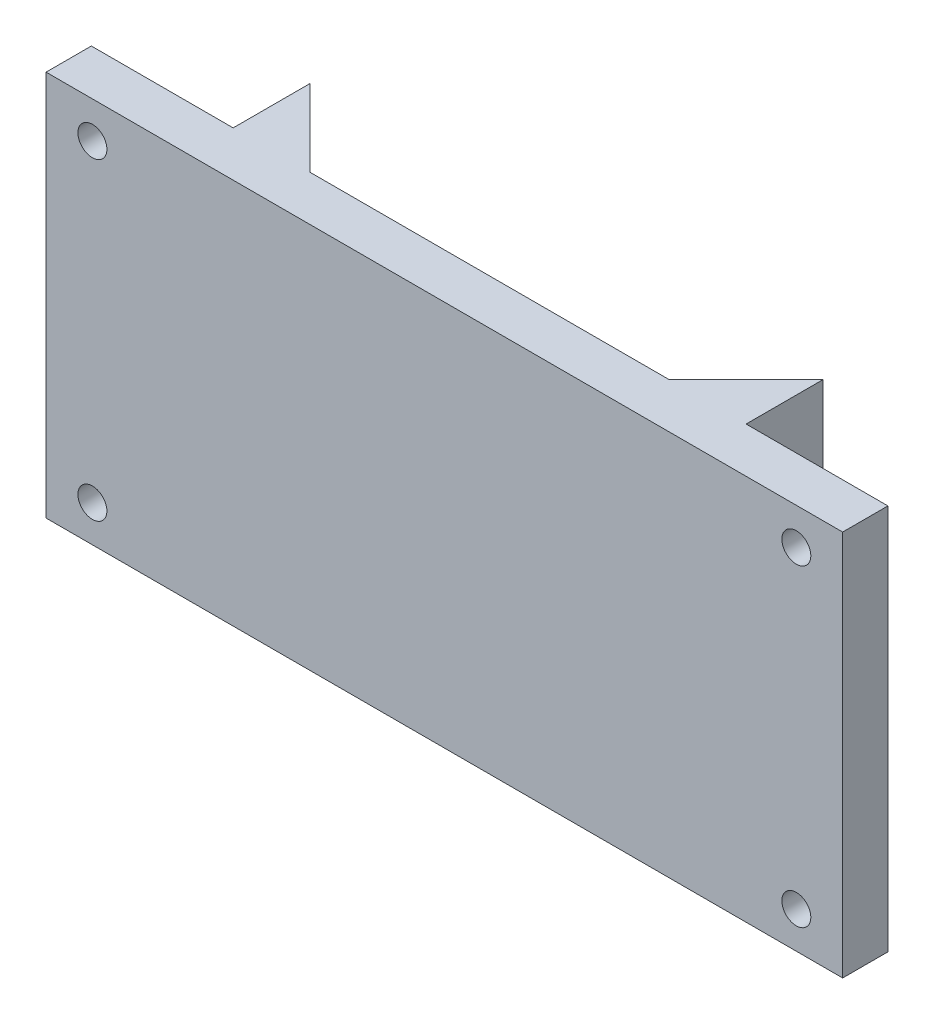
SolidWorks part; units mm, degrees
ref_plane "Front Plane" through (0, 0, 0) normal (0, 0, 1) x (1, 0, 0)
ref_plane "Top Plane" through (0, 0, 0) normal (0, 1, 0) x (1, 0, 0)
ref_plane "Right Plane" through (0, 0, 0) normal (1, 0, 0) x (0, 0, -1)
sketch "Sketch1" plane through (0, 0, 0) normal (0, 0, 1) x (1, 0, 0)
  line L1 (-25, -16) -> (25, -16)
  line L2 (-25, -16) -> (-25, 16)
  line L3 (-25, 16) -> (25, 16)
  line L4 (25, -16) -> (25, 16)
  line L5 (-25, -16) -> (25, 16) construction
  line L6 (-25, 16) -> (25, -16) construction
  point P0 (0, 0)
  dimension "D1" = 32
  dimension "D2" = 50
extrude "Boss-Extrude1" add sketch "Sketch1" along normal blind 3.75
sketch "Sketch2" plane through (0, 16, 0) normal (0, 1, 0) x (1, 0, 0)
  line L0 (-21.25, 0) -> (-21.25, 6.364)
  line L1 (25, 0) -> (-25, 0) construction
  line L2 (-21.25, 6.364) -> (-14.886, 0)
  line L3 (-14.886, 0) -> (-21.25, 0)
  line L4 (-25, -3.75) -> (-25, 0) construction
  line L5 (0, 0) -> (0, 9.0579) construction
  line L6 (14.886, 0) -> (21.25, 0)
  line L7 (21.25, 6.364) -> (14.886, 0)
  line L8 (21.25, 0) -> (21.25, 6.364)
  dimension "D1" = 3.75
  dimension "D2" = 9
extrude "Boss-Extrude2" add sketch "Sketch2" against normal up to surface (32 mm away) up to face at (0, -16, 1.875)
sketch "Sketch4" plane through (0, 16, 0) normal (0, 1, 0) x (1, 0, 0)
  line L1 (25, -3.75) -> (33, -3.75)
  line L2 (25, -3.75) -> (25, 0)
  line L3 (25, 0) -> (33, 0)
  line L4 (33, -3.75) -> (33, 0)
  line L5 (-25, -3.75) -> (-33, -3.75)
  line L6 (-25, -3.75) -> (-25, 0)
  line L7 (-25, 0) -> (-33, 0)
  line L8 (-33, -3.75) -> (-33, 0)
  dimension "D1" = 8
extrude "Boss-Extrude3" add sketch "Sketch4" against normal up to surface (32 mm away) up to face at (0, -16, -0.5228)
hole_wizard "M2 Clearance Hole1" positions "Sketch5" profile "Sketch6" hole size "M2" standard "ISO" end condition up to next
sketch "Sketch5" plane through (0, 0, 3.75) normal (0, 0, 1) x (1, 0, 0)
  point P0 (-29.1617, -12.975)
  point P3 (-29.1617, 12.975)
sketch "Sketch6" plane through (-29.1617, -12.975, 3.75) normal (1, 0, 0) x (0, -1, 0)
  line L0 (0, 0) -> (0, 3.751)
  line L1 (0, 3.751) -> (1.2, 3.751)
  line L2 (1.2, 3.751) -> (1.2, 0)
  line L5 (1.2, 0) -> (0, 0)
  line L11 (0, -6.35) -> (0, 107.95) construction
  dimension "Thru Hole Dia." = 2.4
  dimension "Thru Hole Depth" = 3.751
mirror "Mirror1" about plane through (0, 0, 0) normal (1, 0, 0) of "M2 Clearance Hole1"
